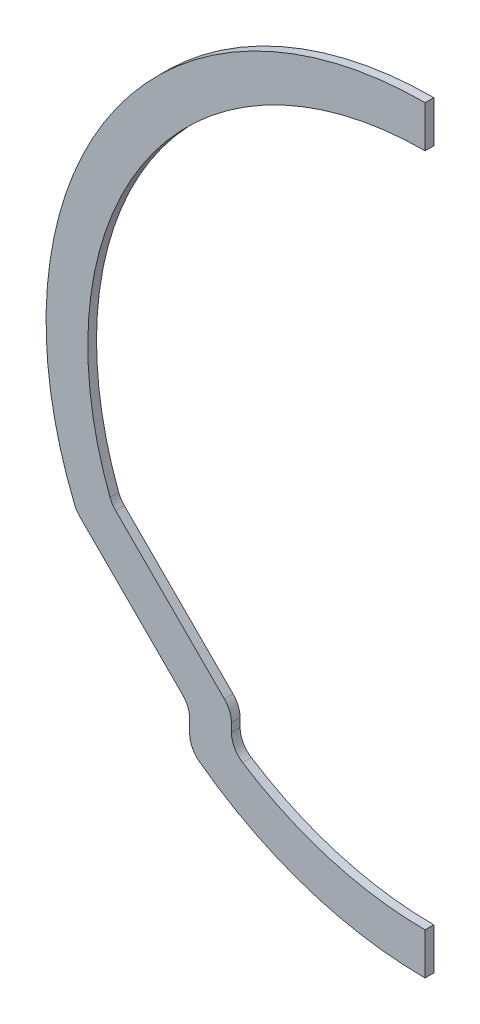
SolidWorks part; units mm, degrees
material "Balsa"
ref_plane "Front Plane" through (0, 0, 0) normal (0, 0, 1) x (1, 0, 0)
ref_plane "Top Plane" through (0, 0, 0) normal (0, 1, 0) x (1, 0, 0)
ref_plane "Right Plane" through (0, 0, 0) normal (1, 0, 0) x (0, 0, -1)
sketch "Sketch1" plane through (0, 0, 0) normal (0, 0, 1) x (1, 0, 0)
  line L0 (0, 32.094) -> (0, -346.2619) construction
  line L1 (0, 0) -> (0, 244.345) construction
  line L2 (0, 0) -> (0, 471.6969) construction
  line L3 (0, 0) -> (-283.5939, 0) construction
  line L4 (-127.2933, -32.5553) -> (-85.9841, -73.8644)
  line L5 (-85.9841, -73.8644) -> (-85.9841, -86.6438)
  line L6 (-85.9841, -73.8644) -> (-54.3993, -105.4493) construction
  arc A0 (-54.3993, -105.4493) -> (-127.2933, -32.5553) centre (0, 21.844) ccw
  arc A2 (-82.075, -89.6305) -> (-54.3993, -105.4493) centre (0, 21.844) ccw construction
  arc A3 (-127.2933, -32.5553) -> (-82.075, -89.6305) centre (0, 21.844) ccw construction
  arc A4 (-85.9841, -86.6438) -> (-54.3993, -105.4493) centre (0, 21.844) ccw
  spline S2 degree 3 poles (-1530.9406, -7642.7149) (259.0907, -1408.3953) (378.6573, 10.519) (49.9381, 150.9258) (45.7097, 152.4909) (37.1079, 155.2035) (32.7346, 156.3511) (27.1752, 157.5183) (26.0587, 157.7384) (23.8163, 158.1514) (22.6888, 158.3447) (19.306, 158.8811) (17.0511, 159.1813) (10.2867, 159.9126) (1.2693, 160.4377) (-7.745, 160.0789) (-14.5046, 159.4749) (-16.7575, 159.2176) (-20.1367, 158.7464) (-21.263, 158.5751) (-23.5156, 158.2037) (-24.6421, 158.0036) (-30.2426, 156.9366) (-34.6466, 155.8674) (-43.3063, 153.3113) (-47.562, 151.8242) (-55.9254, 148.4331) (-60.0331, 146.529) (-66.0807, 143.3516) (-68.0818, 142.2359) (-72.0044, 139.9197) (-73.9301, 138.7173) (-79.6017, 134.9792) (-86.884, 129.6473) (-93.6143, 123.6295) (-98.4521, 118.8554) (-100.0296, 117.2204) (-102.3424, 114.7015) (-103.1054, 113.8496) (-104.6077, 112.1297) (-105.3467, 111.2623) (-108.9818, 106.8875) (-111.6981, 103.2683) (-116.7574, 95.7975) (-119.1004, 91.9459) (-123.4121, 84.0098) (-125.3809, 79.9253) (-127.6006, 74.6695) (-128.0327, 73.61) (-128.8681, 71.4874) (-129.2719, 70.423) (-130.4422, 67.2205) (-131.1674, 65.0732) (-133.1812, 58.5951) (-135.4347, 49.861) (-136.834, 40.9354) (-137.5569, 34.168) (-137.7434, 31.9) (-137.9397, 28.4793) (-137.9911, 27.3374) (-138.0656, 25.0596) (-138.0887, 23.9223) (-138.135, 18.2442) (-137.9496, 13.7276) (-137.1441, 4.7454) (-136.5239, 0.2797) (-134.8456, -8.6005) (-133.7876, -13.015) (-131.2181, -21.791) (-129.7278, -26.0794) (-126.351, -34.4622) (-124.4643, -38.5569) (-120.2966, -46.5538) (-118.0156, -50.456) (-114.9122, -55.2108) (-114.2789, -56.1556) (-112.9868, -58.0327) (-112.3272, -58.9661) (-110.315, -61.7398) (-108.9333, -63.5482) (-104.6702, -68.8537) (-98.6716, -75.6089) (-92.0553, -81.7381) (-86.8592, -86.0978) (-85.0881, -87.5114) (-82.3719, -89.5716) (-81.4566, -90.2482) (-79.6058, -91.5811) (-78.6696, -92.238) (312.7351, -359.6403) (1980.7618, 1435.5712) (5240.7041, 5800.1077) knots -2.409432 -2.409432 -2.409432 -2.409432 0.03125 0.03125 0.0625 0.0625 0.09375 0.09375 0.101563 0.101563 0.109375 0.109375 0.125 0.125 0.15625 0.1875 0.1875 0.203125 0.203125 0.210937 0.210937 0.21875 0.21875 0.25 0.25 0.28125 0.28125 0.3125 0.3125 0.328125 0.328125 0.34375 0.34375 0.375 0.40625 0.40625 0.421875 0.421875 0.429687 0.429687 0.4375 0.4375 0.46875 0.46875 0.5 0.5 0.53125 0.53125 0.539062 0.539062 0.546875 0.546875 0.5625 0.5625 0.59375 0.625 0.625 0.640625 0.640625 0.648437 0.648437 0.65625 0.65625 0.6875 0.6875 0.71875 0.71875 0.75 0.75 0.78125 0.78125 0.8125 0.8125 0.84375 0.84375 0.851562 0.851562 0.859375 0.859375 0.875 0.875 0.90625 0.9375 0.9375 0.953125 0.953125 0.960937 0.960937 0.96875 0.96875 4.2021 4.2021 4.2021 4.2021 only from (66.3397, 143.1887) to (-66.0465, -100.0388)
  spline S3 degree 3 poles (66.3397, 143.1887) (62.3323, 145.3909) (58.2494, 147.3758) (49.9381, 150.9258) (45.7097, 152.4909) (37.1079, 155.2035) (32.7346, 156.3511) (27.1752, 157.5183) (26.0587, 157.7384) (23.8163, 158.1514) (22.6888, 158.3447) (19.306, 158.8811) (17.0511, 159.1813) (10.2867, 159.9126) (1.2693, 160.4377) (-7.745, 160.0789) (-14.5046, 159.4749) (-16.7575, 159.2176) (-20.1367, 158.7464) (-21.263, 158.5751) (-23.5156, 158.2037) (-24.6421, 158.0036) (-30.2426, 156.9366) (-34.6466, 155.8674) (-43.3063, 153.3113) (-47.562, 151.8242) (-55.9254, 148.4331) (-60.0331, 146.529) (-66.0807, 143.3516) (-68.0818, 142.2359) (-72.0044, 139.9197) (-73.9301, 138.7173) (-79.6017, 134.9792) (-86.884, 129.6473) (-93.6143, 123.6295) (-98.4521, 118.8554) (-100.0296, 117.2204) (-102.3424, 114.7015) (-103.1054, 113.8496) (-104.6077, 112.1297) (-105.3467, 111.2623) (-108.9818, 106.8875) (-111.6981, 103.2683) (-116.7574, 95.7975) (-119.1004, 91.9459) (-123.4121, 84.0098) (-125.3809, 79.9253) (-127.6006, 74.6695) (-128.0327, 73.61) (-128.8681, 71.4874) (-129.2719, 70.423) (-130.4422, 67.2205) (-131.1674, 65.0732) (-133.1812, 58.5951) (-135.4347, 49.861) (-136.834, 40.9354) (-137.5569, 34.168) (-137.7434, 31.9) (-137.9397, 28.4793) (-137.9911, 27.3374) (-138.0656, 25.0596) (-138.0887, 23.9223) (-138.135, 18.2442) (-137.9496, 13.7276) (-137.1441, 4.7454) (-136.5239, 0.2797) (-134.8456, -8.6005) (-133.7876, -13.015) (-131.2181, -21.791) (-129.7278, -26.0794) (-127.6847, -31.1513) (-127.3213, -32.0275) (-126.9491, -32.8995) knots 0 0 0 0 0.03125 0.03125 0.0625 0.0625 0.09375 0.09375 0.101563 0.101563 0.109375 0.109375 0.125 0.125 0.15625 0.1875 0.1875 0.203125 0.203125 0.210937 0.210937 0.21875 0.21875 0.25 0.25 0.28125 0.28125 0.3125 0.3125 0.328125 0.328125 0.34375 0.34375 0.375 0.40625 0.40625 0.421875 0.421875 0.429687 0.429687 0.4375 0.4375 0.46875 0.46875 0.5 0.5 0.53125 0.53125 0.539062 0.539062 0.546875 0.546875 0.5625 0.5625 0.59375 0.625 0.625 0.640625 0.640625 0.648437 0.648437 0.65625 0.65625 0.6875 0.6875 0.71875 0.71875 0.75 0.75 0.78125 0.78125 0.787815 0.787815 0.787815 0.787815 construction
  point P2 (0, 160.2226)
  point P3 (0, -116.9127)
  point P23 (-85.9841, -73.8644)
  dimension "D1" = 277.1353
  dimension "D2" = 276.86
  dimension "D3" = 21.844
  dimension "D5" = 45
  dimension "D6" = 113.03
  dimension "D4" = 58.42
  dimension "D7" = 45
extrude "Boss-Extrude1" add sketch "Sketch1" along normal mid plane 3.175
sketch "Sketch2" plane through (0, 0, 1.5875) normal (0, 0, 1) x (1, 0, 0)
  line L4 (-114.3729, -23.9231) -> (-70.7441, -67.5518)
  line L5 (-70.7441, -67.5518) -> (-70.7441, -79.0076)
  line L6 (-114.3729, -23.9231) -> (-70.7441, -67.5518)
  line L7 (-70.7441, -67.5518) -> (-70.7441, -79.0076)
  arc A2 (-70.7441, -79.0076) -> (-114.3729, -23.9231) centre (0, 21.844) ccw
  arc A3 (-70.7441, -79.0076) -> (-114.3729, -23.9231) centre (0, 21.844) ccw
  dimension "D1" = 15.24
extrude "Cut-Extrude1" cut sketch "Sketch2" against normal up to surface (3.175 mm away) up to face at (-27.5361, -9.1994, -1.5875)
fillet "Fillet1" radius 8.89 6 edges at (-127.2933, -32.5553, 0) (-114.3729, -23.9231, 0) (-85.9841, -73.8644, 0) (-85.9841, -86.6438, 0) (-70.7441, -67.5518, 0) (-70.7441, -79.0076, 0)
sketch "Sketch3" plane through (0, 0, 1.5875) normal (0, 0, 1) x (1, 0, 0)
  line L0 (-0.0002, 49.9919) -> (-0.0176, 733.2) construction
  line L1 (-0.0002, 49.9919) -> (-0.0176, 733.2) construction
  line L2 (-136.2041, -28.3557) -> (-0.0002, 49.9919) construction
  line L3 (136.2076, -28.3488) -> (-0.0002, 49.9919) construction
  line L4 (-136.2041, -28.3557) -> (-0.0002, 49.9919) construction
  line L5 (136.2076, -28.3488) -> (-0.0002, 49.9919) construction
  line L6 (-1.6539, 152.6441) -> (-1.654, 160.2641)
  line L7 (1.6481, 152.6442) -> (1.648, 160.2642)
  line L8 (-1.6539, 152.6441) -> (1.6481, 152.6442)
  line L9 (119.8485, -45.962) -> (106.7537, -38.3747)
  line L10 (121.4435, -43.2066) -> (108.3479, -35.6188)
  line L11 (-126.0584, -33.7901) -> (-88.588, -71.2606)
  line L12 (-85.9841, -77.5468) -> (-85.9841, -82.2574)
  line L13 (-126.0584, -33.7901) -> (-88.588, -71.2606) construction
  line L14 (-85.9841, -77.5468) -> (-85.9841, -82.2574) construction
  line L18 (121.4435, -43.2066) -> (108.3479, -35.6188)
  line L30 (-123.167, -47.8929) -> (-104.8722, -37.2914)
  line L35 (119.8485, -45.962) -> (106.7537, -38.3747)
  line L47 (108.5244, -35.721) -> (120.1169, -46.1175) construction
  line L48 (114.3206, -40.9193) -> (126.5619, -48.0121) construction
  line L49 (113.8577, -42.5592) -> (122.0137, -47.2849)
  line L50 (115.5132, -39.7021) -> (123.6691, -44.4278)
  line L51 (113.8577, -42.5592) -> (115.5132, -39.7021)
  line L52 (122.0137, -47.2849) -> (123.6691, -44.4278)
  line L58 (-124.7703, -45.1423) -> (-106.4681, -34.5364)
  line L59 (-124.7703, -45.1423) -> (-123.167, -47.8929)
  line L71 (-124.7703, -45.1423) -> (-123.167, -47.8929) construction
  line L72 (-124.7703, -45.1423) -> (-106.4681, -34.5364) construction
  line L73 (-123.167, -47.8929) -> (-104.8722, -37.2914) construction
  line L74 (-123.167, -47.8929) -> (-107.9499, -35.3951) construction
  line L75 (-115.5584, -41.644) -> (-110.9064, -38.9482) construction
  line L76 (-119.3826, -41.9518) -> (-112.6266, -38.0369)
  line L77 (-117.727, -44.8088) -> (-110.971, -40.8938)
  line L78 (-119.3826, -41.9518) -> (-117.727, -44.8088)
  line L79 (-112.6266, -38.0369) -> (-110.971, -40.8938)
  arc A0 (-54.3993, -105.4493) -> (-127.2933, -32.5553) centre (0, 21.844) ccw construction
  arc A2 (-1.654, 160.2641) -> (-130.2816, -24.9489) centre (0, 21.844) ccw construction
  arc A3 (-130.2816, -24.9489) -> (-127.2933, -32.5553) centre (0, 21.844) ccw construction
  arc A4 (-1.654, 160.2641) -> (-130.2816, -24.9489) centre (0, 21.844) ccw construction
  arc A5 (-130.2816, -24.9489) -> (-127.9919, -30.8906) centre (0, 21.844) ccw construction
  arc A6 (-82.3849, -89.4016) -> (-127.9919, -30.8906) centre (0, 21.844) ccw
  arc A7 (-127.9919, -30.8906) -> (-126.0584, -33.7901) centre (-119.7722, -27.504) ccw
  arc A8 (-85.9841, -77.5468) -> (-88.588, -71.2606) centre (-94.8741, -77.5468) ccw
  arc A9 (-85.9841, -82.2574) -> (-82.3849, -89.4016) centre (-77.0941, -82.2574) ccw
  arc A11 (-127.9919, -30.8906) -> (-126.0584, -33.7901) centre (-119.7722, -27.504) ccw construction
  arc A12 (-85.9841, -77.5468) -> (-88.588, -71.2606) centre (-94.8741, -77.5468) ccw construction
  arc A13 (-85.9841, -82.2574) -> (-82.3849, -89.4016) centre (-77.0941, -82.2574) ccw construction
  arc A14 (130.2841, -24.9419) -> (1.648, 160.2642) centre (0, 21.844) ccw construction
  arc A15 (1.648, 160.2642) -> (-1.654, 160.2641) centre (0, 21.844) ccw
  arc A16 (130.2841, -24.9419) -> (1.648, 160.2642) centre (0, 21.844) ccw construction
  arc A17 (1.648, 160.2642) -> (-1.654, 160.2641) centre (0, 21.844) ccw
  spline S0 degree 3 poles (106.7537, -38.3747) (107.2851, -37.456) (107.8165, -36.5374) (108.3479, -35.6188) knots 0 0 0 0 1 1 1 1 weights 1 1 1 1
  spline S1 degree 3 poles (119.8485, -45.962) (120.3802, -45.0435) (120.9118, -44.1251) (121.4435, -43.2066) knots 0 0 0 0 1 1 1 1 weights 1 1 1 1
  spline S2 degree 3 poles (-885.9096, -1769.7959) (-211.5315, -623.0099) (457.4335, 532.6653) (1115.294, 1687.3986) knots -628.025755 -628.025755 -628.025755 -628.025755 629.32196 629.32196 629.32196 629.32196 weights 1.00213 0.999289 0.99929 1.002132 only from (119.8485, -45.962) to (121.4435, -43.2066)
  spline S3 degree 3 poles (-1102.963, 1696.4301) (-441.8978, 540.8873) (227.2768, -614.259) (901.012, -1762.8827) knots -628.210575 -628.210575 -628.210575 -628.210575 629.142222 629.142222 629.142222 629.142222 weights 1.001328 0.999558 0.999557 1.001327 only from (-106.4681, -34.5364) to (-104.8722, -37.2914)
  spline S4 degree 3 poles (-106.4681, -34.5364) (-105.9361, -35.4547) (-105.4042, -36.373) (-104.8722, -37.2914) knots 0 0 0 0 1 1 1 1 weights 1 1 1 1 construction
  spline S6 degree 3 poles (-898.3985, -1763.0369) (-224.3104, -615.0446) (444.2624, 540.7506) (1102.1878, 1695.4772) knots -627.922228 -627.922228 -627.922228 -627.922228 629.425892 629.425892 629.425892 629.425892 weights 1.001921 0.999359 0.99936 1.001924 only from (106.7537, -38.3747) to (108.3479, -35.6188)
  point P49 (-116.0256, -43.8229)
  point P50 (120.451, -46.3794)
  arc M19 (-82.3849, -89.4016) -> (-127.9919, -30.8906) centre (0, 21.844) ccw
  line M21 (-126.0584, -33.7901) -> (-88.588, -71.2606)
  dimension "D1" = 3.302
  dimension "D2" = 7.62
  dimension "D4" = 3.302
  dimension "D5" = 7.62
  dimension "D6" = 3.302
  dimension "D7" = 5.842
  dimension "D3" = 0
extrude "Cut-Extrude2" [suppressed] cut sketch "Sketch3" against normal through all contours L79 L76 L77 M21 | L6 L8 L7 M19 | L51 L49 L50 M19
sketch "Sketch4" plane through (0, 0, 0) normal (1, 0, 0) x (0, 0, -1)
  line L1 (-96.2805, 232.7957) -> (122.2438, 232.7957)
  line L2 (-96.2805, 232.7957) -> (-96.2805, -207.8589)
  line L3 (-96.2805, -207.8589) -> (122.2438, -207.8589)
  line L4 (122.2438, 232.7957) -> (122.2438, -207.8589)
extrude "Cut-Extrude3" cut sketch "Sketch4" along normal through all
equation "\"a\"= 0.06"
equation "\"slotwidth\"=0.13"
equation "\"slotheight\"=0.3"
